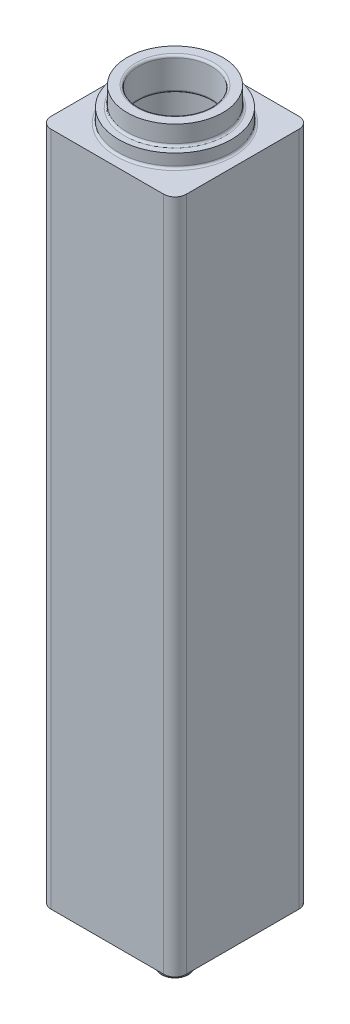
SolidWorks part; units mm, degrees
ref_plane "Plan de face" through (0, 0, 0) normal (0, 0, 1) x (1, 0, 0)
ref_plane "Plan de dessus" through (0, 0, 0) normal (0, 1, 0) x (1, 0, 0)
ref_plane "Plan de droite" through (0, 0, 0) normal (1, 0, 0) x (0, 0, -1)
sketch "Esquisse1" plane through (0, 0, 0) normal (0, 1, 0) x (1, 0, 0)
  line L1 (-60, -60) -> (60, -60)
  line L2 (-60, -60) -> (-60, 60)
  line L3 (-60, 60) -> (60, 60)
  line L4 (60, -60) -> (60, 60)
  line L5 (-60, -60) -> (60, 60) construction
  line L6 (-60, 60) -> (60, -60) construction
  point P0 (0, 0)
  dimension "D1" = 120
  dimension "D2" = 120
extrude "Boss.-Extru.1" add sketch "Esquisse1" along normal blind 600
fillet "Congé1" radius 10 1 edges at (60, 300, 60) type face fillet first side face at (0, 300, 60) second side face at (60, 300, 0)
fillet "Congé2" radius 10 1 edges at (60, 300, -60) type face fillet first side face at (60, 300, -5) second side face at (0, 300, -60)
fillet "Congé3" radius 10 1 edges at (-60, 300, -60) type face fillet first side face at (-5, 300, -60) second side face at (-60, 300, 0)
fillet "Congé4" radius 10 1 edges at (-60, 300, 60) type face fillet first side face at (-60, 300, 5) second side face at (-5, 300, 60)
sketch "Esquisse2" plane through (0, 600, 0) normal (0, 1, 0) x (1, 0, 0)
  circle A0 centre (0, 0) radius 42.5
  dimension "D1" = 85
extrude "Boss.-Extru.2" add sketch "Esquisse2" along normal blind 29
sketch "Esquisse4" plane through (0, 600, 0) normal (0, 1, 0) x (1, 0, 0)
  circle A0 centre (0, 0) radius 50
  dimension "D1" = 100
extrude "Boss.-Extru.3" add sketch "Esquisse4" along normal blind 12
sketch "Esquisse8" plane through (0, 0, 0) normal (0, -1, 0) x (1, 0, 0)
  circle A0 centre (0, 0) radius 45
  dimension "D1" = 90
extrude "Boss.-Extru.4" add sketch "Esquisse8" along normal blind 12
sketch "Esquisse9" plane through (0, 0, 0) normal (0, -1, 0) x (1, 0, 0)
  circle A0 centre (0, 0) radius 12.5
  dimension "D1" = 25
extrude "Boss.-Extru.5" add sketch "Esquisse9" along normal blind 50
sketch "Esquisse5" plane through (0, 600, 0) normal (0, 1, 0) x (1, 0, 0)
  circle A0 centre (0, 0) radius 35
  dimension "D1" = 70
extrude "Enlèv. mat.-Extru.1" cut sketch "Esquisse5" against normal blind 590
fillet "Congé5" radius 2 2 edges at (0, -12, -45) (0, -12, -12.5)
fillet "Congé6" radius 2 1 edges at (0, -50, -12.5)
fillet "Congé7" radius 2 1 edges at (0, 600, -50)
sketch "Esquisse11" plane through (0, 629, 0) normal (0, 1, 0) x (1, 0, 0)
  circle A0 centre (0, 0) radius 32.5
extrude "Enlèv. mat.-Extru.3" cut sketch "Esquisse11" against normal blind 29
fillet "Congé9" radius 2 1 edges at (0, 600, 32.5)
fillet "Congé11" radius 2 1 edges at (0, 612, 42.5)
fillet "Congé12" radius 2 1 edges at (0, 629, 32.5)
